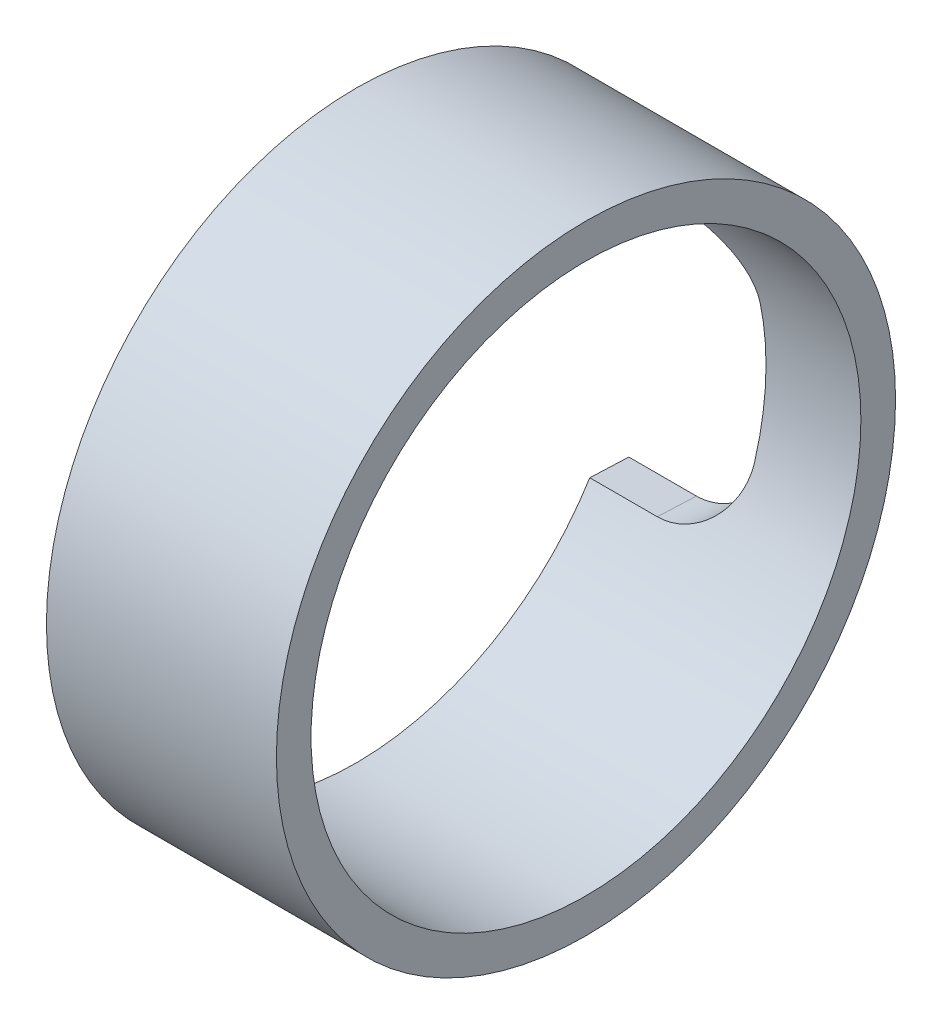
SolidWorks part; units mm, degrees
material "Nylon 6/10"
ref_plane "Front Plane" through (0, 0, 0) normal (0, 0, 1) x (1, 0, 0)
ref_plane "Top Plane" through (0, 0, 0) normal (0, 1, 0) x (1, 0, 0)
ref_plane "Right Plane" through (0, 0, 0) normal (1, 0, 0) x (0, 0, -1)
sketch "Sketch1" plane through (0, 0, 0) normal (0, 0, 1) x (1, 0, 0)
  line L0 (-25.4, 7.5) -> (-42.315, 7.5) construction
  line L1 (-39.013, 8.7312) -> (-32.527, 8.7312)
  line L2 (-39.013, 8.7312) -> (-39.013, 7.754)
  line L3 (-39.013, 7.754) -> (-32.527, 7.754)
  line L4 (-32.527, 8.7312) -> (-32.527, 7.754)
  line L5 (-39.14, 7.7355) -> (-39.14, 12.5132) construction
  line L6 (-32.4, 15.2446) -> (-32.4, -15.2446) construction
  line L7 (0, 0) -> (-47.1489, 0) construction
  dimension "D1" = 0.254
  dimension "D2" = 0.127
  dimension "D3" = 0.127
  dimension "D4" = 17.4625
revolve "Revolve1" add sketch "Sketch1" angle 360 about L7
ref_plane "Plane1" through (0, 0, 0) normal (0, -0.0407, -0.9992) x (1, 0, 0)
sketch "Sketch3" plane through (0, 0, 0) normal (0, -0.0407, -0.9992) x (1, 0, 0)
  line L0 (-39.013, 3.81) -> (-39.013, -3.81)
  line L1 (-39.013, 7.754) -> (-39.013, -7.754) construction
  line L2 (-39.013, -3.81) -> (-37.108, -3.81)
  line L3 (-35.203, -1.905) -> (-35.203, 1.905)
  line L4 (-37.108, 3.81) -> (-39.013, 3.81)
  line L5 (-39.013, 8.7312) -> (-39.013, -8.7312) construction
  line L6 (-39.013, 8.7312) -> (-39.013, -8.7312) construction
  line L7 (-35.203, 0) -> (-39.013, 0) construction
  arc A0 (-37.108, -3.81) -> (-35.203, -1.905) centre (-37.108, -1.905) ccw
  arc A1 (-35.203, 1.905) -> (-37.108, 3.81) centre (-37.108, 1.905) ccw
  dimension "D1" = 7.62
  dimension "D2" = 3.81
extrude "Cut-Extrude1" cut sketch "Sketch3" along normal up to next
